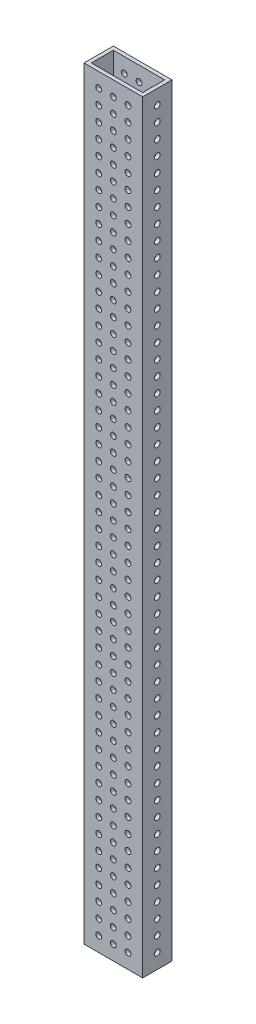
SolidWorks part; units mm, degrees
ref_plane "Front Plane" through (0, 0, 0) normal (0, 0, 1) x (1, 0, 0)
ref_plane "Top Plane" through (0, 0, 0) normal (0, 1, 0) x (1, 0, 0)
ref_plane "Right Plane" through (0, 0, 0) normal (1, 0, 0) x (0, 0, -1)
sketch "Sketch1" plane through (0, 0, 0) normal (0, 1, 0) x (1, 0, 0)
  line L0 (3.175, 22.225) -> (47.625, 22.225)
  line L1 (0, 0) -> (50.8, 0)
  line L2 (0, 0) -> (0, 25.4)
  line L3 (0, 25.4) -> (50.8, 25.4)
  line L4 (50.8, 0) -> (50.8, 25.4)
  line L5 (47.625, 3.175) -> (47.625, 22.225)
  line L6 (3.175, 3.175) -> (47.625, 3.175)
  line L7 (3.175, 3.175) -> (3.175, 22.225)
  dimension "D1" = 50.8
  dimension "D2" = 25.4
  dimension "D3" = 3.175
extrude "Boss-Extrude1" add sketch "Sketch1" along normal mid plane 660.4
sketch "Sketch2" plane through (0, 0, 0) normal (0, 0, 1) x (1, 0, 0)
  line L2 (0, 330.2) -> (50.8, 330.2) construction
  line L3 (0, 330.2) -> (0, -330.2) construction
  circle A291 centre (12.7, 317.5) radius 2.4892
  dimension "D1" = 12.7
  dimension "D2" = 12.7
  dimension "D3" = 4.9784
extrude "Cut-Extrude1" cut sketch "Sketch2" against normal through all
pattern_linear "LPattern1" count 51 spacing 12.7 along (0, -1, 0) count 3 spacing 12.7 along (1, 0, 0) of "Cut-Extrude1"
sketch "Sketch3" plane through (50.8, 0, 0) normal (1, 0, 0) x (0, 0, -1)
  line L0 (0, 330.2) -> (0, -330.2) construction
  line L1 (0, 330.2) -> (25.4, 330.2) construction
  circle A0 centre (12.7, 317.5) radius 2.4892
  dimension "D1" = 4.9784
  dimension "D2" = 12.7
  dimension "D3" = 12.7
extrude "Cut-Extrude2" cut sketch "Sketch3" against normal through all
pattern_linear "LPattern2" count 51 spacing 12.7 along (0, -1, 0) of "Cut-Extrude2"
